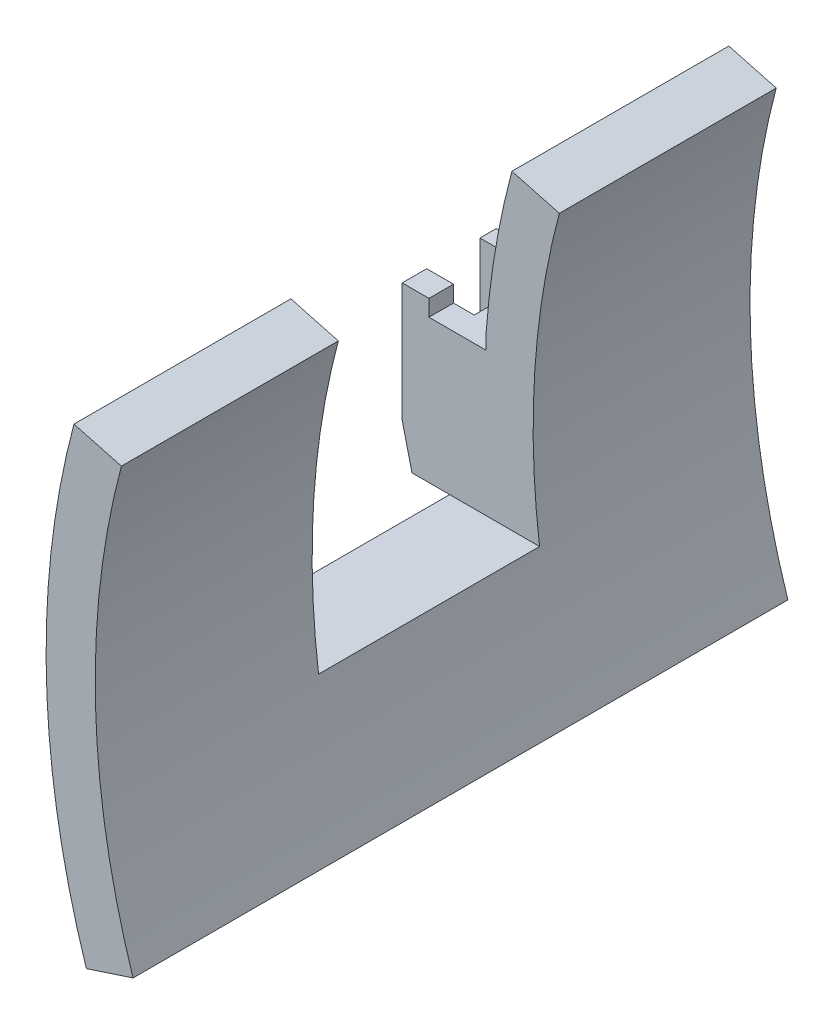
SolidWorks part; units mm, degrees
ref_plane "Front Plane" through (0, 0, 0) normal (0, 0, 1) x (1, 0, 0)
ref_plane "Top Plane" through (0, 0, 0) normal (0, 1, 0) x (1, 0, 0)
ref_plane "Right Plane" through (0, 0, 0) normal (1, 0, 0) x (0, 0, -1)
sketch "Sketch3" plane through (0, 0, 0) normal (0, 0, 1) x (1, 0, 0)
  line L0 (-95.0813, -30.9767) -> (0, 0) construction
  line L1 (0, 0) -> (-96.5926, 25.8819) construction
  line L2 (-90.797, 24.329) -> (-96.5926, 25.8819)
  line L3 (-89.3764, -29.1181) -> (-95.0813, -30.9767)
  line L4 (0, 0) -> (94.4973, 0)
  arc A0 (-96.5926, 25.8819) -> (-95.0813, -30.9767) centre (0, 0) ccw
  arc A1 (-90.797, 24.329) -> (-89.3764, -29.1181) centre (0, 0) ccw
  dimension "D1" = 100
  dimension "D3" = 6
  dimension "D2" = 55
  dimension "D4" = 165
extrude "Boss-Extrude2" add sketch "Sketch3" along normal blind 40 and the other way blind 40 contours A1 L2 A0 L3 region at (-95.6579, -2.5426, 0)
ref_plane "Plane2" through (-100, 0, 0) normal (-1, 0, 0) x (0, 0, 1)
sketch "Sketch5" plane through (-100, 0, 0) normal (-1, 0, 0) x (0, 0, 1)
  line L1 (-25, 7.3648) -> (25, 7.3648)
  line L2 (-25, 7.3648) -> (-25, -22.6352)
  line L3 (-25, -22.6352) -> (25, -22.6352)
  line L4 (25, 7.3648) -> (25, -22.6352)
  line L5 (-25, 7.3648) -> (25, -22.6352) construction
  line L6 (-25, -22.6352) -> (25, 7.3648) construction
  line L10 (-34.7926, -55.9949) -> (34.7926, -55.9949) construction
  line L11 (36.4262, 17.3648) -> (-36.4262, 17.3648) construction
  line L14 (-40, -30.9767) -> (40, -30.9767)
  line L15 (40, -30.9767) -> (40, 25.8819)
  line L16 (40, 25.8819) -> (-40, 25.8819)
  line L17 (-40, 25.8819) -> (-40, -30.9767)
  line L18 (-40, -30.9767) -> (40, -30.9767)
  line L19 (40, -30.9767) -> (40, 25.8819)
  line L20 (40, 25.8819) -> (-40, 25.8819)
  line L21 (-40, 25.8819) -> (-40, -30.9767)
  point P0 (0, -7.6352)
  point P9 (0, 17.3648)
  dimension "D2" = 10
  dimension "D3" = 30
  dimension "D4" = 50
  dimension "D5" = 0
extrude "Boss-Extrude1" add sketch "Sketch5" along normal blind 10 and the other way blind 4 contours L4 L1 L2 L3 region at (-100, -7.6352, 0)
sketch "Sketch6" plane through (-110, 0, 0) normal (-1, 0, 0) x (0, 0, 1)
  line L1 (-23, 7.3648) -> (-16.5, 7.3648)
  line L2 (-23, 7.3648) -> (-23, -18.8352)
  line L3 (-23, -18.8352) -> (-16.5, -18.8352)
  line L4 (-16.5, 7.3648) -> (-16.5, -18.8352)
  line L5 (23, 7.3648) -> (16.5, 7.3648)
  line L6 (23, 7.3648) -> (23, -18.8352)
  line L7 (23, -18.8352) -> (16.5, -18.8352)
  line L8 (16.5, 7.3648) -> (16.5, -18.8352)
  line L9 (16.5, -18.8352) -> (-16.5, -18.8352)
  line L10 (16.5, -18.8352) -> (16.5, -12.1352)
  line L11 (16.5, -12.1352) -> (-16.5, -12.1352)
  line L12 (-16.5, -18.8352) -> (-16.5, -12.1352)
  line L13 (-25, 7.3648) -> (25, 7.3648) construction
  point P10 (0, -12.1352)
  dimension "D1" = 6.5
  dimension "D2" = 6.7
  dimension "D3" = 26.2
  dimension "D5" = 33
extrude "Cut-Extrude1" cut sketch "Sketch6" against normal blind 5.8 contours L8 L11 L4 L9 | L4 L1 L2 L3 | L5 L8 L7 L6 region at (-110, -5.7352, -19.75) region at (-110, -15.4852, 0) region at (-110, -5.7352, 19.75)
sketch "Sketch7" plane through (0, 0, -25) normal (0, 0, -1) x (-1, 0, 0)
  line L0 (108.2, -22.6352) -> (108.2, -14.6352)
  line L1 (97.4046, -22.6352) -> (110, -22.6352) construction
  line L2 (108.2, -14.6352) -> (110, -7.1352)
  line L3 (110, 7.3648) -> (110, -22.6352) construction
  line L4 (110, -7.1352) -> (110, -22.6352)
  line L5 (110, -22.6352) -> (108.2, -22.6352)
  dimension "D1" = 15.5
  dimension "D2" = 1.8
  dimension "D3" = 8
extrude "Cut-Extrude2" cut sketch "Sketch7" against normal up to surface (50 mm away) up to face at (-104.567, -7.6572, 25)
sketch "Sketch8" plane through (0, 0, -25) normal (0, 0, -1) x (-1, 0, 0)
  line L1 (99.7284, 5.3648) -> (106.7284, 5.3648)
  line L2 (106.7284, 5.3648) -> (106.7284, 7.3648)
  line L3 (99.7284, 7.3648) -> (106.7284, 7.3648)
  line L5 (99.7284, 7.3648) -> (110, 7.3648) construction
  line L6 (99.7284, 5.3648) -> (99.7284, 7.3648)
  dimension "D1" = 2
  dimension "D2" = 7
extrude "Cut-Extrude3" cut sketch "Sketch8" against normal up to surface (50 mm away) up to face at (-105.778, -8.7332, 25)
sketch "Sketch9" plane through (-110, 0, 0) normal (-1, 0, 0) x (0, 0, 1)
  line L1 (-13.5, 31.6264) -> (13.5, 31.6264)
  line L2 (-13.5, 31.6264) -> (-13.5, -12.1352)
  line L3 (-13.5, -12.1352) -> (13.5, -12.1352)
  line L4 (13.5, 31.6264) -> (13.5, -12.1352)
  line L5 (16.5, -12.1352) -> (-16.5, -12.1352) construction
  line L6 (16.5, -12.1352) -> (-16.5, -12.1352)
  line L7 (-16.5, 7.3648) -> (-16.5, -7.1352) construction
  line L8 (16.5, 7.3648) -> (16.5, -7.1352) construction
  line M5 (-16.5, -7.1352) -> (16.5, -7.1352)
  line M7 (16.5, 7.3648) -> (-16.5, 7.3648)
  dimension "D1" = 3
  dimension "D2" = 3
extrude "Cut-Extrude4" cut sketch "Sketch9" against normal through all contours L4 L2 M7 M5 | L4 L2 L3 M5 | L4 L1 L2 M7 region at (-110, 19.4956, 0) region at (-110, 0.1148, 0) region at (-110, -9.6352, 0)
